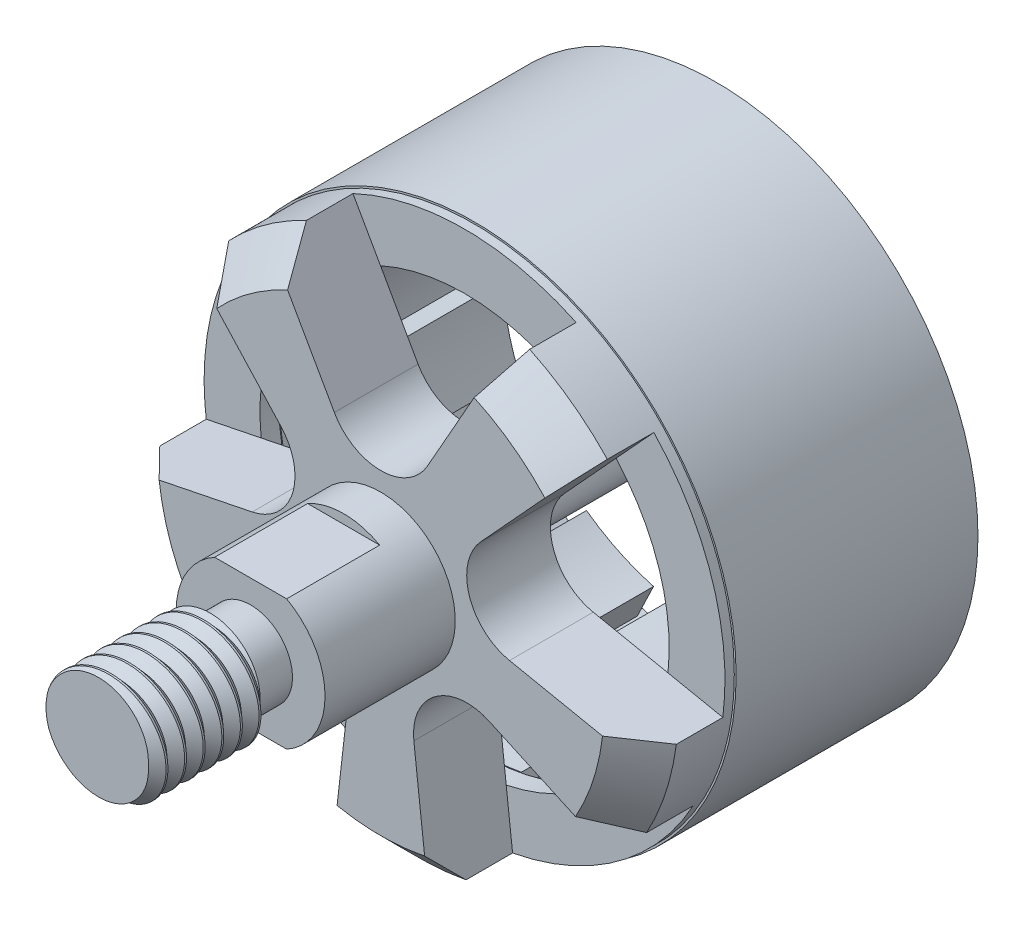
SolidWorks part; units mm, degrees
material "6061 Alloy"
ref_plane "Front" through (0, 0, 0) normal (0, 0, 1) x (1, 0, 0)
ref_plane "Top" through (0, 0, 0) normal (0, 1, 0) x (1, 0, 0)
ref_plane "Right" through (0, 0, 0) normal (1, 0, 0) x (0, 0, -1)
sketch "Sketch2" plane through (0, 0, 0) normal (0, 1, 0) x (1, 0, 0)
  line L0 (0, 62.9307) -> (0, -62.9307) construction
  line L1 (14, 33) -> (14, 17)
  line L2 (14, 17) -> (12, 15)
  line L3 (12, 15) -> (4, 15)
  line L4 (4, 15) -> (4, 8)
  line L7 (4, 8) -> (2.25, 8)
  line L8 (2.25, 8) -> (2.25, 6)
  line L9 (2.25, 6) -> (3, 6)
  line L10 (3, 6) -> (3, 0)
  line L11 (3, 0) -> (0, 0)
  line L12 (14, 19.5) -> (1.5, 19.5) construction
  line L13 (14, 33) -> (13, 33)
  line L14 (13, 33) -> (13, 19.5)
  line L15 (13, 19.5) -> (1.5, 19.5)
  line L16 (0, 40.5) -> (0, 0)
  line L17 (0, 40.5) -> (1.5, 40.5)
  line L18 (1.5, 40.5) -> (1.5, 19.5)
  dimension "D1" = 6
  dimension "D2" = 6
  dimension "D3" = 2
  dimension "D4" = 7
  dimension "D6" = 4.5
  dimension "D7" = 2
  dimension "D8" = 45
  dimension "D9" = 4.5
  dimension "D11" = 8
  dimension "D12" = 28
  dimension "D13" = 33
  dimension "D14" = 1
  dimension "D15" = 3
  dimension "D16" = 40.5
revolve "Revolve1" add sketch "Sketch2" angle 360 about L0
sketch "Sketch3" plane through (0, 0, -15) normal (0, 0, 1) x (1, 0, 0)
  line L0 (-6, 12.6491) -> (-2.5, 6.4585)
  line L1 (2.5, 6.4585) -> (6, 12.6491)
  line L2 (10.1759, 9.6151) -> (5.3698, 4.3734)
  line L3 (6.9149, -0.3819) -> (13.8841, -1.7975)
  line L4 (12.2891, -6.7066) -> (5.8187, -3.7555)
  line L5 (1.7737, -6.6945) -> (2.5809, -13.7601)
  line L6 (-2.5809, -13.7601) -> (-1.7737, -6.6945)
  line L7 (-5.8187, -3.7555) -> (-12.2891, -6.7066)
  line L8 (-13.8841, -1.7975) -> (-6.9149, -0.3819)
  line L9 (-5.3698, 4.3734) -> (-10.1759, 9.6151)
  arc A1 (2.5, 6.4585) -> (-2.5, 6.4585) centre (0, 7.8719) cw
  circle A2 centre (0, 0) radius 14 construction
  arc A3 (6, 12.6491) -> (-6, 12.6491) centre (0, 0) ccw
  arc A4 (13.8841, -1.7975) -> (10.1759, 9.6151) centre (0, 0) ccw
  arc A5 (6.9149, -0.3819) -> (5.3698, 4.3734) centre (7.4866, 2.4325) cw
  arc A6 (2.5809, -13.7601) -> (12.2891, -6.7066) centre (0, 0) ccw
  arc A7 (1.7737, -6.6945) -> (5.8187, -3.7555) centre (4.627, -6.3685) cw
  arc A8 (-12.2891, -6.7066) -> (-2.5809, -13.7601) centre (0, 0) ccw
  arc A9 (-5.8187, -3.7555) -> (-1.7737, -6.6945) centre (-4.627, -6.3685) cw
  arc A10 (-10.1759, 9.6151) -> (-13.8841, -1.7975) centre (0, 0) ccw
  arc A11 (-5.3698, 4.3734) -> (-6.9149, -0.3819) centre (-7.4866, 2.4325) cw
  point P8 (0, 2.0366)
  point P9 (0, 5)
  point P10 (0, 14)
  point P34 (0, 0)
  dimension "D1" = 5
  dimension "D2" = 12
  dimension "D3" = 9
  dimension "D4" = 5
extrude "Cut-Extrude1" cut sketch "Sketch3" against normal blind 4.5
sketch "Sketch4" plane through (0, 0, -19.5) normal (0, 0, -1) x (-1, 0, 0)
  circle A0 centre (0, 0) radius 13
  arc A1 (-9.4982, 8.876) -> (-12.9014, -1.5979) centre (0, 0) ccw construction
  circle A2 centre (0, 0) radius 11
  circle A3 centre (0, 0) radius 14 construction
  dimension "D1" = 3
extrude "Boss-Extrude1" add sketch "Sketch4" along normal blind 1
ref_plane "Plane1" through (0, 0, -32.55) normal (0, 0, -1) x (-1, 0, 0)
sketch "Sketch5" plane through (0, 0, -32.55) normal (0, 0, -1) x (-1, 0, 0)
  line L0 (-2, 12.8452) -> (-2, 10.8167)
  line L1 (2, 12.8452) -> (2, 10.8167)
  line L2 (3.7714, 12.4409) -> (2.8912, 10.6132)
  line L3 (7.3753, 10.7054) -> (6.4951, 8.8777)
  line L4 (8.7958, 9.5725) -> (7.2098, 8.3077)
  line L5 (11.2898, 6.4452) -> (9.7038, 5.1804)
  line L6 (12.0781, 4.8082) -> (10.1004, 4.3568)
  line L7 (12.9682, 0.9085) -> (10.9905, 0.4571)
  line L8 (12.9682, -0.9085) -> (10.9905, -0.4571)
  line L9 (12.0781, -4.8082) -> (10.1004, -4.3568)
  line L10 (11.2898, -6.4452) -> (9.7038, -5.1804)
  line L11 (8.7958, -9.5725) -> (7.2098, -8.3077)
  line L12 (7.3753, -10.7054) -> (6.4951, -8.8777)
  line L13 (3.7714, -12.4409) -> (2.8912, -10.6132)
  line L14 (2, -12.8452) -> (2, -10.8167)
  line L15 (-2, -12.8452) -> (-2, -10.8167)
  line L16 (-3.7714, -12.4409) -> (-2.8912, -10.6132)
  line L17 (-7.3753, -10.7054) -> (-6.4951, -8.8777)
  line L18 (-8.7958, -9.5725) -> (-7.2098, -8.3077)
  line L19 (-11.2898, -6.4452) -> (-9.7038, -5.1804)
  line L20 (-12.0781, -4.8082) -> (-10.1004, -4.3568)
  line L21 (-12.9682, -0.9085) -> (-10.9905, -0.4571)
  line L22 (-12.9682, 0.9085) -> (-10.9905, 0.4571)
  line L23 (-12.0781, 4.8082) -> (-10.1004, 4.3568)
  line L24 (-11.2898, 6.4452) -> (-9.7038, 5.1804)
  line L25 (-8.7958, 9.5725) -> (-7.2098, 8.3077)
  line L26 (-7.3753, 10.7054) -> (-6.4951, 8.8777)
  line L27 (-3.7714, 12.4409) -> (-2.8912, 10.6132)
  circle A0 centre (0, 0) radius 13 construction
  arc A1 (2, 12.8452) -> (-2, 12.8452) centre (0, 0) ccw
  arc A2 (2, 10.8167) -> (-2, 10.8167) centre (0, 0) ccw
  arc A3 (6.4951, 8.8777) -> (2.8912, 10.6132) centre (0, 0) ccw
  arc A4 (7.3753, 10.7054) -> (3.7714, 12.4409) centre (0, 0) ccw
  arc A5 (9.7038, 5.1804) -> (7.2098, 8.3077) centre (0, 0) ccw
  arc A6 (11.2898, 6.4452) -> (8.7958, 9.5725) centre (0, 0) ccw
  arc A7 (10.9905, 0.4571) -> (10.1004, 4.3568) centre (0, 0) ccw
  arc A8 (12.9682, 0.9085) -> (12.0781, 4.8082) centre (0, 0) ccw
  arc A9 (10.1004, -4.3568) -> (10.9905, -0.4571) centre (0, 0) ccw
  arc A10 (12.0781, -4.8082) -> (12.9682, -0.9085) centre (0, 0) ccw
  arc A11 (7.2098, -8.3077) -> (9.7038, -5.1804) centre (0, 0) ccw
  arc A12 (8.7958, -9.5725) -> (11.2898, -6.4452) centre (0, 0) ccw
  arc A13 (2.8912, -10.6132) -> (6.4951, -8.8777) centre (0, 0) ccw
  arc A14 (3.7714, -12.4409) -> (7.3753, -10.7054) centre (0, 0) ccw
  arc A15 (-2, -10.8167) -> (2, -10.8167) centre (0, 0) ccw
  arc A16 (-2, -12.8452) -> (2, -12.8452) centre (0, 0) ccw
  arc A17 (-6.4951, -8.8777) -> (-2.8912, -10.6132) centre (0, 0) ccw
  arc A18 (-7.3753, -10.7054) -> (-3.7714, -12.4409) centre (0, 0) ccw
  arc A19 (-9.7038, -5.1804) -> (-7.2098, -8.3077) centre (0, 0) ccw
  arc A20 (-11.2898, -6.4452) -> (-8.7958, -9.5725) centre (0, 0) ccw
  arc A21 (-10.9905, -0.4571) -> (-10.1004, -4.3568) centre (0, 0) ccw
  arc A22 (-12.9682, -0.9085) -> (-12.0781, -4.8082) centre (0, 0) ccw
  arc A23 (-10.1004, 4.3568) -> (-10.9905, 0.4571) centre (0, 0) ccw
  arc A24 (-12.0781, 4.8082) -> (-12.9682, 0.9085) centre (0, 0) ccw
  arc A25 (-7.2098, 8.3077) -> (-9.7038, 5.1804) centre (0, 0) ccw
  arc A26 (-8.7958, 9.5725) -> (-11.2898, 6.4452) centre (0, 0) ccw
  arc A27 (-2.8912, 10.6132) -> (-6.4951, 8.8777) centre (0, 0) ccw
  arc A28 (-3.7714, 12.4409) -> (-7.3753, 10.7054) centre (0, 0) ccw
  point P61 (0, 0)
  dimension "D1" = 2
  dimension "D2" = 4
  dimension "D3" = 4
  dimension "D4" = 14
extrude "Boss-Extrude2" add sketch "Sketch5" against normal blind 12 separate body
sketch "Sketch6" plane through (0, 0, -8) normal (0, 0, 1) x (1, 0, 0)
  line L0 (0, 4.5) -> (0, 3.5) construction
  line L1 (-2.446, 4.5) -> (2.446, 4.5)
  line L2 (-2.446, 4.5) -> (-2.446, 3.5)
  line L3 (-2.446, 3.5) -> (2.446, 3.5)
  line L4 (2.446, 4.5) -> (2.446, 3.5)
  line L5 (-8.6687, 0) -> (10.2569, 0) construction
  line L6 (0, -3.5) -> (0, -4.5) construction
  line L7 (-2.446, -3.5) -> (2.446, -3.5)
  line L8 (-2.446, -3.5) -> (-2.446, -4.5)
  line L9 (-2.446, -4.5) -> (2.446, -4.5)
  line L10 (2.446, -3.5) -> (2.446, -4.5)
  line L11 (0, 3.5) -> (0, -3.5) construction
  arc A1 (5.8187, -3.7555) -> (1.7737, -6.6945) centre (4.627, -6.3685) ccw construction
  dimension "D1" = 7
  dimension "D2" = 1
extrude "Cut-Extrude2" cut sketch "Sketch6" against normal blind 5
sketch "Sketch7" plane through (0, 0, 0) normal (0, 0, 1) x (1, 0, 0)
  circle A1 centre (0, 0) radius 3
  circle A2 centre (0, 0) radius 3
  dimension "D1" = 0
curve "Helix/Spiral1" pitch 1 height 6 turns 6
sketch "Sketch9" plane through (0, 0, 0) normal (0, 1, 0) x (1, 0, 0)
  line L0 (2.5, 6) -> (3.05, 6.4949)
  line L1 (3.05, 6.4949) -> (3.05, 5.5051)
  line L2 (3.05, 5.5051) -> (2.5, 6)
  line L3 (0, 0) -> (0, 6.6678) construction
  line L4 (2.5, 6) -> (3.05, 6) construction
  point P2 (3.05, 6)
  point P12 (3, 6)
  dimension "D1" = 5
  dimension "D2" = 0.9898
  dimension "D3" = 0.55
sweep "Cut-Sweep1" cut profiles "Sketch9" path "Helix/Spiral1"
sketch "Sketch10" plane through (0, 0, -33) normal (0, 0, -1) x (-1, 0, 0)
  circle A0 centre (0, 0) radius 14 construction
  circle A1 centre (0, 0) radius 14
  circle A2 centre (0, 0) radius 14.1
  dimension "D1" = 0.1
extrude "Boss-Extrude3" add sketch "Sketch10" against normal blind 13 separate body
sketch "Sketch11" plane through (0, 0, 0) normal (0, 1, 0) x (1, 0, 0)
  line L0 (0, 40.5) -> (0, 42.6408) construction
  line L1 (1.5, 40.5) -> (-1.5, 40.5) construction
  line L3 (-1.75, 39.5) -> (-1.25, 39.5)
  line L4 (-1.75, 39.5) -> (-1.75, 39)
  line L5 (-1.75, 39) -> (-1.25, 39)
  line L6 (-1.25, 39.5) -> (-1.25, 39)
  dimension "D1" = 0.5
  dimension "D2" = 1
  dimension "D3" = 2.5
revolve "Cut-Revolve1" cut sketch "Sketch11" angle 360 about L0
